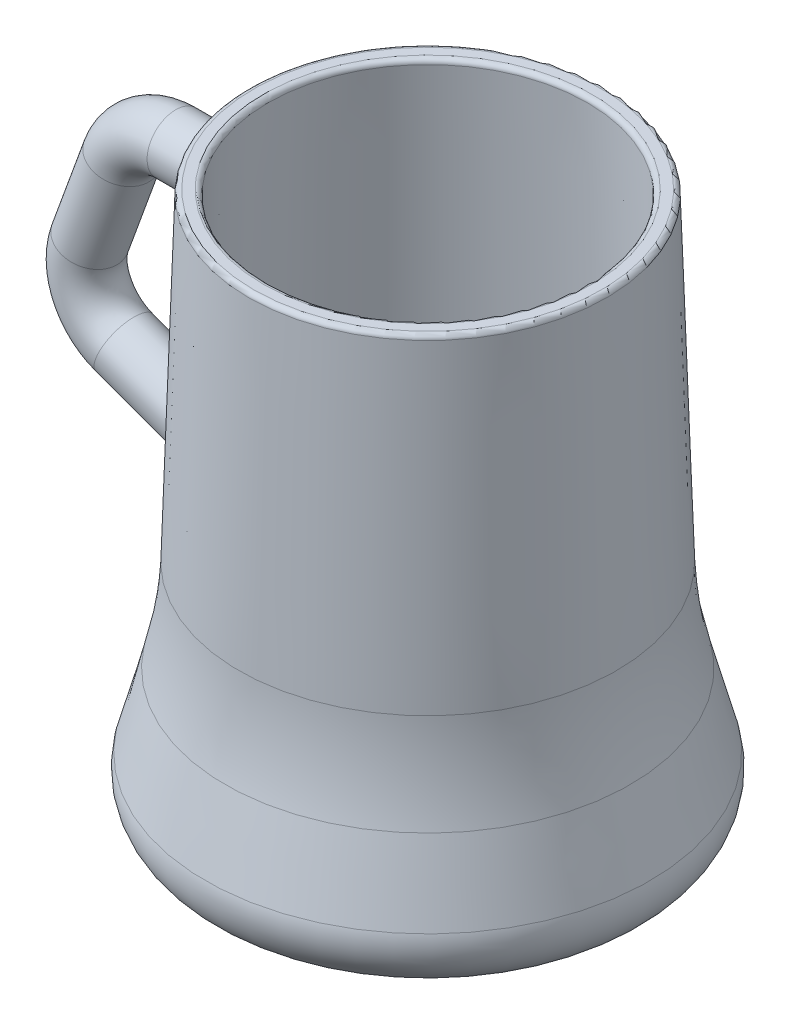
SolidWorks part; units mm, degrees
ref_plane "Front Plane" through (0, 0, 0) normal (0, 0, 1) x (1, 0, 0)
ref_plane "Top Plane" through (0, 0, 0) normal (0, 1, 0) x (1, 0, 0)
ref_plane "Right Plane" through (0, 0, 0) normal (1, 0, 0) x (0, 0, -1)
sketch "Sketch1" plane through (0, 0, 0) normal (1, 0, 0) x (0, 0, -1)
  line L0 (0, 0) -> (36.9677, 0)
  line L1 (46.627, 12.5882) -> (42.4973, 28.0004)
  line L2 (0, 0) -> (0, 33.2165) construction
  line L3 (39.6436, 47.3096) -> (37.5, 115)
  line L4 (0, 4) -> (36.9677, 4)
  line L5 (42.7633, 11.5529) -> (38.6336, 26.9651)
  line L6 (37.5, 115) -> (33.5, 115)
  line L7 (35.6456, 47.183) -> (33.502, 114.8734) construction
  line L8 (33.5, 115) -> (35.6456, 47.183)
  line L9 (0, 4) -> (0, 0)
  line L10 (33.5, 115) -> (0, 115)
  line L11 (0, 115) -> (0, 4)
  arc A0 (42.4973, 28.0004) -> (39.6436, 47.3096) centre (124.601, 50) cw
  arc A1 (46.627, 12.5882) -> (36.9677, 0) centre (36.9677, 10) cw
  arc A2 (42.7633, 11.5529) -> (36.9677, 4) centre (36.9677, 10) cw
  arc A3 (38.6336, 26.9651) -> (35.6456, 47.183) centre (124.601, 50) cw
  point P11 (50, 0)
  dimension "D1" = 85
  dimension "D4" = 50
  dimension "D7" = 10
  dimension "D2" = 50
  dimension "D3" = 75
  dimension "D5" = 37.5
  dimension "D6" = 115
  dimension "D9" = 4
  dimension "D8" = 4
revolve "Revolve2" add sketch "Sketch1" angle 360 about L2 region at (0, 2, -1.2422) region at (0, 57.3557, -18.2613)
sketch "Sketch3" plane through (0, 0, 0) normal (0, 0, 1) x (1, 0, 0)
  line L0 (0, 141.6081) -> (0, 73.5676) construction
  line L1 (0, 97) -> (-52.9167, 97)
  line L2 (-64.193, 89.1042) -> (-70.8958, 70.6886)
  line L3 (-63.7237, 55.3081) -> (0, 32.1145)
  line L4 (37.5, 115) -> (-37.5, 115) construction
  arc A0 (-63.7237, 55.3081) -> (-70.8958, 70.6886) centre (-59.6194, 66.5844) cw
  arc A1 (-64.193, 89.1042) -> (-52.9167, 97) centre (-52.9167, 85) cw
  point P4 (0, 32.1145)
  point P12 (-75, 59.4123)
  point P15 (-61.3192, 97)
  dimension "D5" = 12
  dimension "D6" = 12
  dimension "D1" = 18
  dimension "D2" = 110
  dimension "D3" = 75
  dimension "D4" = 40
sweep "Sweep1" add path "Sketch3" circular profile diameter 12 parameters "D3"=12
sketch "Sketch14" plane through (0, 0, 0) normal (0, 0, 1) x (1, 0, 0)
  line L0 (0, -178.173) -> (0, 409.4295) construction
  line L1 (0, 0) -> (36.9677, 0)
  line L2 (46.627, 12.5882) -> (42.4973, 28.0004)
  line L3 (39.6436, 47.3096) -> (37.5, 115)
  line L4 (0, 4) -> (36.9677, 4)
  line L5 (42.7633, 11.5529) -> (38.6336, 26.9651)
  line L6 (35.6456, 47.183) -> (33.1545, 125.8459)
  line L7 (35.6456, 47.183) -> (33.502, 114.8734) construction
  line L8 (0, 4) -> (36.9677, 4) construction
  line L9 (33.1545, 125.8459) -> (0, 125.8459)
  line L11 (0, 125.8459) -> (0, 4)
  arc A0 (42.4973, 28.0004) -> (39.6436, 47.3096) centre (124.601, 50) cw
  arc A1 (46.627, 12.5882) -> (36.9677, 0) centre (36.9677, 10) cw
  arc A2 (42.7633, 11.5529) -> (36.9677, 4) centre (36.9677, 10) cw
  arc A3 (38.6336, 26.9651) -> (35.6456, 47.183) centre (124.601, 50) cw
  point P11 (50, 0)
  point P20 (0, 125.8459)
  point P21 (0, 4)
  dimension "D3" = 85
  dimension "D6" = 115
  dimension "D7" = 10
  dimension "D1" = 50
  dimension "D2" = 75
  dimension "D4" = 50
  dimension "D5" = 37.5
  dimension "D8" = 4
revolve "Cut-Revolve22" cut sketch "Sketch14" angle 360 about L0 region at (18.1296, 62.5437, 0)
fillet "Fillet1" radius 1 2 edges at (0, 115, -37.5) (0, 115, 33.498)
fillet "Fillet2" radius 2 3 edges at (-39.4676, 52.8642, -0.0724) (-40.1509, 40.3451, 0.1462) (-37.6244, 100.133, 5.1171)
